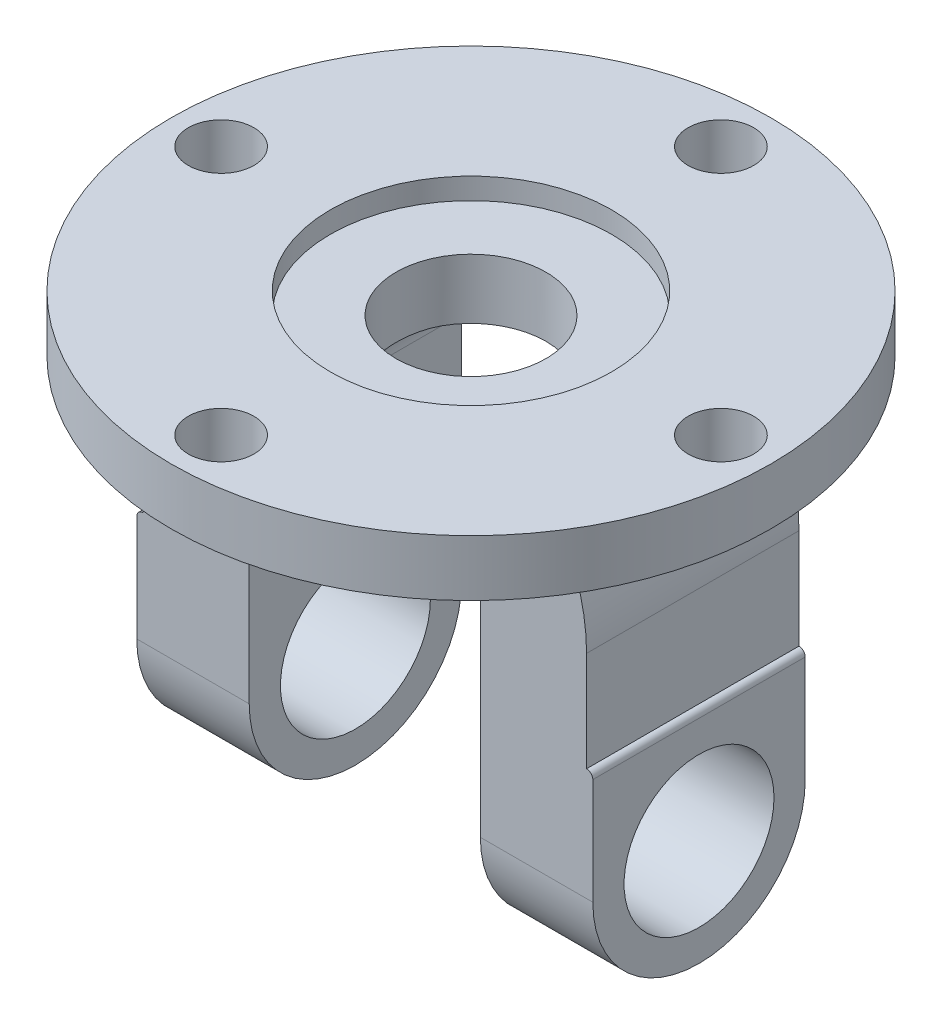
SolidWorks part; units mm, degrees
ref_plane "Front Plane" through (0, 0, 0) normal (0, 0, 1) x (1, 0, 0)
ref_plane "Top Plane" through (0, 0, 0) normal (0, 1, 0) x (1, 0, 0)
ref_plane "Right Plane" through (0, 0, 0) normal (1, 0, 0) x (0, 0, -1)
sketch "Sketch1" plane through (0, 0, 0) normal (0, 1, 0) x (1, 0, 0)
  circle A0 centre (0, 0) radius 48
  circle A1 centre (0, 0) radius 40 construction
  circle A3 centre (0, 40) radius 5.25
  circle A4 centre (40, 0) radius 5.25
  circle A5 centre (0, -40) radius 5.25
  circle A6 centre (-40, 0) radius 5.25
  point P16 (0, 0)
  dimension "D1" = 96
  dimension "D2" = 80
  dimension "D4" = 10.5
  dimension "D5" = 4
extrude "Boss-Extrude1" add sketch "Sketch1" along normal blind 9
sketch "Sketch2" plane through (0, 9, 0) normal (0, 1, 0) x (1, 0, 0)
  circle A0 centre (0, 0) radius 22.5
  dimension "D1" = 45
extrude "Cut-Extrude1" cut sketch "Sketch2" against normal blind 3.4
sketch "Sketch3" plane through (0, 5.6, 0) normal (0, 1, 0) x (1, 0, 0)
  circle A0 centre (0, 0) radius 12
  dimension "D1" = 24
extrude "Cut-Extrude2" cut sketch "Sketch3" against normal through all
sketch "Sketch4" plane through (0, 0, 0) normal (0, 0, 1) x (1, 0, 0)
  line L2 (-36.5, -66) -> (-36.5, -32)
  line L3 (31.5, 0) -> (-31.5, 0)
  line L6 (-35.5, -67) -> (-19.5, -67)
  line L7 (-18.5, -66) -> (-18.5, -12)
  line L8 (-10.5, -4) -> (10.5, -4)
  line L11 (-35.5, -31) -> (-35.5, -15)
  line L12 (0, -84.3119) -> (0, 0) construction
  line L13 (35.5, -31) -> (35.5, -15)
  line L14 (18.5, -66) -> (18.5, -12)
  line L15 (35.5, -67) -> (19.5, -67)
  line L17 (36.5, -66) -> (36.5, -32)
  arc A1 (-31.5, 0) -> (-35.5, -15) centre (-5.375, -15) ccw
  arc A3 (-18.5, -12) -> (-10.5, -4) centre (-10.5, -12) cw
  arc A4 (18.5, -12) -> (10.5, -4) centre (10.5, -12) ccw
  arc A5 (31.5, 0) -> (35.5, -15) centre (5.375, -15) cw
  arc A6 (35.5, -31) -> (36.5, -32) centre (35.5, -32) cw
  arc A7 (35.5, -67) -> (36.5, -66) centre (35.5, -66) ccw
  arc A8 (18.5, -66) -> (19.5, -67) centre (19.5, -66) ccw
  arc A9 (-19.5, -67) -> (-18.5, -66) centre (-19.5, -66) ccw
  arc A10 (-36.5, -66) -> (-35.5, -67) centre (-35.5, -66) ccw
  arc A11 (-36.5, -32) -> (-35.5, -31) centre (-35.5, -32) cw
  point P5 (0, -4)
  point P29 (36.5, -67)
  point P32 (18.5, -67)
  point P35 (-18.5, -67)
  point P38 (-36.5, -67)
  dimension "D1" = 1
  dimension "D2" = 63
  dimension "D3" = 55
  dimension "D4" = 36
  dimension "D5" = 4
  dimension "D6" = 73
  dimension "D7" = 18
  dimension "D8" = 71
  dimension "D9" = 15
  dimension "D10" = 4
extrude "Boss-Extrude2" add sketch "Sketch4" along normal blind 17 and the other way blind 17
sketch "Sketch5" plane through (0, -4, 0) normal (0, -1, 0) x (1, 0, 0)
  circle A0 centre (0, 0) radius 12
extrude "Cut-Extrude3" cut sketch "Sketch5" against normal blind 4.5 and the other way blind 4.5
sketch "Sketch7" plane through (-36.5, 0, 0) normal (-1, 0, 0) x (0, 0, 1)
  line L0 (-17, 0) -> (-17, -49)
  line L1 (-17, -32) -> (-17, -66) construction
  line L2 (17, -32) -> (17, -66) construction
  line L3 (17, -49) -> (17, 0)
  line L4 (17, 0) -> (31.5546, 0)
  line L5 (-48, 0) -> (48, 0) construction
  line L6 (31.5546, 0) -> (31.5546, -74.2982)
  line L7 (31.5546, -74.2982) -> (-29.7429, -74.2982)
  line L8 (-29.7429, -74.2982) -> (-29.7429, 0)
  line L9 (-29.7429, 0) -> (-17, 0)
  arc A0 (-17, -49) -> (17, -49) centre (0, -49) ccw
extrude "Cut-Extrude4" cut sketch "Sketch7" against normal through all both and the other way through all
sketch "Sketch8" plane through (36.5, 0, 0) normal (1, 0, 0) x (0, 0, -1)
  circle A0 centre (0, -49) radius 12
  arc A1 (-17, -49) -> (17, -49) centre (0, -49) ccw construction
  dimension "D1" = 24
extrude "Cut-Extrude5" cut sketch "Sketch8" against normal through all both
